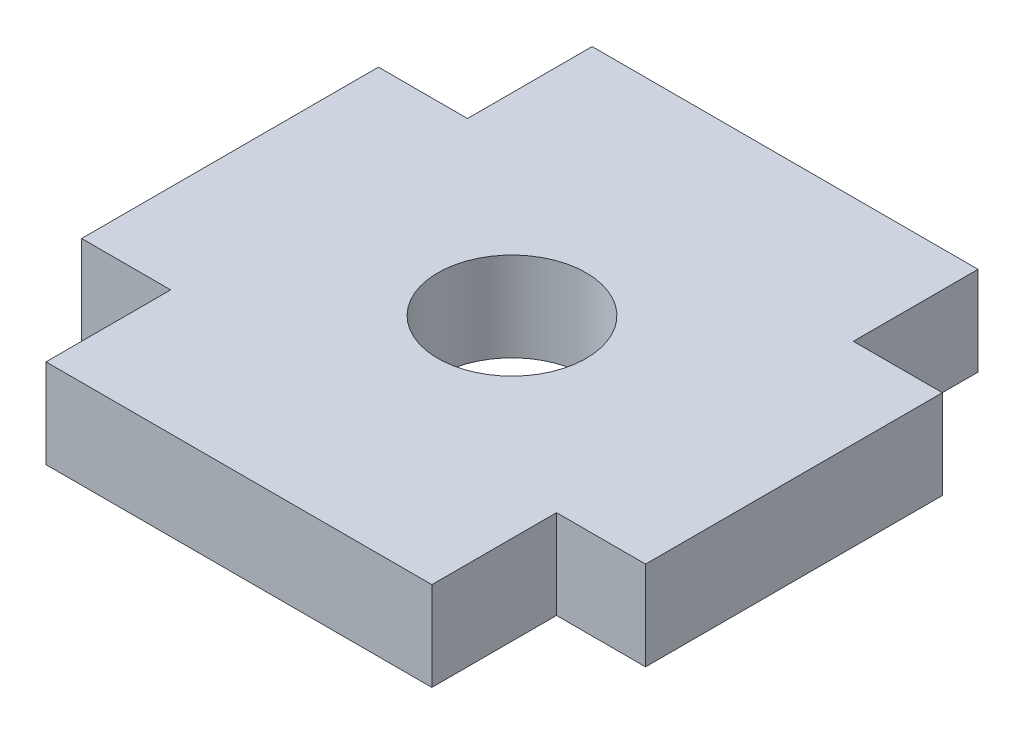
SolidWorks part; units mm, degrees
material "MDF"
ref_plane "Plano frontal" through (0, 0, 0) normal (0, 0, 1) x (1, 0, 0)
ref_plane "Plano superior" through (0, 0, 0) normal (0, 1, 0) x (1, 0, 0)
ref_plane "Plano direito" through (0, 0, 0) normal (1, 0, 0) x (0, 0, -1)
ref_plane "Plano1" through (0, 10, 0) normal (0, -1, 0) x (1, 0, 0)
sketch "Esboço1" plane through (0, 10, 0) normal (0, -1, 0) x (1, 0, 0)
  line L0 (-63.5, -9.1999) -> (-63.5, -5)
  line L1 (-63.5, -5) -> (-60.5, -5)
  line L2 (-60.5, -5) -> (-60.5, 5)
  line L3 (-60.5, 5) -> (-63.5, 5)
  line L4 (-63.5, 5) -> (-63.5, 9.1999)
  line L5 (-63.5, 9.1999) -> (-76.5, 9.1999)
  line L6 (-76.5, 9.1999) -> (-76.5, 5)
  line L7 (-76.5, 5) -> (-79.5, 5)
  line L8 (-79.5, 5) -> (-79.5, -5)
  line L9 (-79.5, -5) -> (-76.5, -5)
  line L10 (-76.5, -5) -> (-76.5, -9.1999)
  line L11 (-76.5, -9.1999) -> (-63.5, -9.1999)
  line L12 (-63.5, 9.1999) -> (-76.5, -9.1999) construction
  line L13 (-63.5, -9.1999) -> (-76.5, 9.1999) construction
  circle A0 centre (-70, 0) radius 2.5
  dimension "D7" = 5
  dimension "D1" = 13
  dimension "D2" = 4.1999
  dimension "D3" = 4.1999
  dimension "D4" = 3
  dimension "D5" = 10
  dimension "D6" = 3
extrude "Ressalto-extrusão1" add sketch "Esboço1" against normal blind 3
